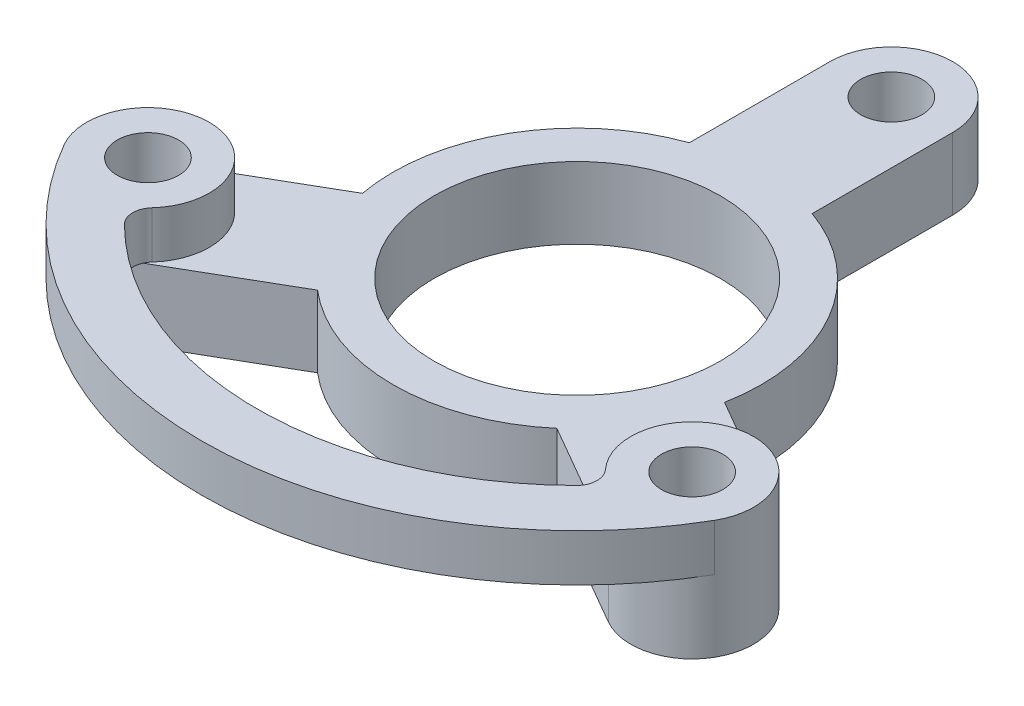
SolidWorks part; units mm, degrees
ref_plane "Front" through (0, 0, 0) normal (0, 0, 1) x (1, 0, 0)
ref_plane "Top" through (0, 0, 0) normal (0, 1, 0) x (1, 0, 0)
ref_plane "Right" through (0, 0, 0) normal (1, 0, 0) x (0, 0, -1)
sketch "Sketch1" plane through (0, 0, 0) normal (0, 1, 0) x (1, 0, 0)
  line L0 (0, 15.3575) -> (-13.3, -7.6788) construction
  line L1 (-13.3, -7.6788) -> (13.3, -7.6788) construction
  line L2 (13.3, -7.6788) -> (0, 15.3575) construction
  line L3 (-3, 8.4853) -> (-3, 15.3575)
  line L4 (3, 8.4853) -> (3, 15.3575)
  line L5 (8.8485, -1.6446) -> (14.8, -5.0807)
  line L6 (5.8485, -6.8407) -> (11.8, -10.2768)
  line L7 (-5.8485, -6.8407) -> (-11.8, -10.2768)
  line L8 (-8.8485, -1.6446) -> (-14.8, -5.0807)
  circle A0 centre (0, 0) radius 9
  circle A1 centre (0, 0) radius 15.3575 construction
  circle A2 centre (0, 15.3575) radius 3
  circle A3 centre (-13.3, -7.6788) radius 3
  circle A4 centre (13.3, -7.6788) radius 3
  circle A5 centre (0, 0) radius 7
  circle A6 centre (0, 15.3575) radius 1.5
  circle A7 centre (13.3, -7.6788) radius 1.5
  circle A8 centre (-13.3, -7.6788) radius 1.5
  point P25 (0, 0)
  dimension "D1" = 18
  dimension "D2" = 6
  dimension "D5" = 14
  dimension "D6" = 3
  dimension "D3" = 26.6
  dimension "D4" = 3
extrude "Boss-Extrude1" add sketch "Sketch1" along normal blind 3.5 contours A0 A5 | A2 L3 A0 L4 | A2 A6 | A3 L7 A0 L8 | A3 A8 | A4 L5 A0 L6 | A4 A7 region at (0, 0, -10.9668) region at (0, 0, -8.7454) region at (0, 0, -18.2727) region at (-9.4976, 0, 5.4834) region at (-11.8424, 0, 5.1542) region at (9.4976, 0, 5.4834) region at (15.8246, 0, 6.2212)
sketch "Sketch2" plane through (0, 3.5, 0) normal (0, 1, 0) x (1, 0, 0)
  line L0 (-13.3, -7.6788) -> (-15.8981, -9.1788) construction
  line L1 (-13.3, -7.6788) -> (-10.7019, -6.1788) construction
  line L2 (-17.3629, -5.9605) -> (-11.688, -4.0124) construction
  line L3 (17.3629, -5.9605) -> (11.688, -4.0124) construction
  arc A0 (-15.8981, -9.1788) -> (15.8981, -9.1788) centre (0, 0) ccw
  arc A1 (-14.8, -5.0807) -> (-11.8, -10.2768) centre (-13.3, -7.6788) ccw construction
  arc A2 (-14.8, -5.0807) -> (-11.8, -10.2768) centre (-13.3, -7.6788) ccw
  arc A3 (-10.7019, -6.1788) -> (10.7019, -6.1788) centre (0, 0) ccw
  arc A4 (11.8, -10.2768) -> (14.8, -5.0807) centre (13.3, -7.6788) ccw construction
  arc A5 (11.8, -10.2768) -> (14.8, -5.0807) centre (13.3, -7.6788) ccw
  arc A6 (17.3629, -5.9605) -> (-17.3629, -5.9605) centre (0, 0) ccw construction
  arc A7 (11.688, -4.0124) -> (-11.688, -4.0124) centre (0, 0) ccw construction
  arc A8 (11.8, -10.2768) -> (-11.8, -10.2768) centre (0, 0) cw
  circle A9 centre (13.3, -7.6788) radius 3
  circle A10 centre (-13.3, -7.6788) radius 3
  arc A11 (-11.688, -4.0124) -> (-10.7019, -6.1788) centre (0, 0) ccw construction
  arc A12 (-17.3629, -5.9605) -> (-15.8981, -9.1788) centre (0, 0) ccw construction
  arc A13 (15.8981, -9.1788) -> (17.3629, -5.9605) centre (0, 0) ccw construction
  arc A14 (10.7019, -6.1788) -> (11.688, -4.0124) centre (0, 0) ccw construction
  line M9 (5.8485, -6.8407) -> (11.8, -10.2768)
  arc M10 (11.8, -10.2768) -> (14.8, -5.0807) centre (13.3, -7.6788) ccw
  arc M18 (-14.8, -5.0807) -> (-11.8, -10.2768) centre (-13.3, -7.6788) ccw
  line M19 (-11.8, -10.2768) -> (-5.8485, -6.8407)
  circle M20 centre (13.3, -7.6788) radius 1.5
  circle M22 centre (-13.3, -7.6788) radius 1.5
extrude "Boss-Extrude2" add sketch "Sketch2" along normal blind 2.3 contours A0 M9 M19 M18 M10 | A10 M18 M22 | A9 M10 M20 region at (-14.1621, 3.5, 10.8962) region at (-16.1158, 3.5, 6.9243) region at (14.0545, 3.5, 10.4946)
fillet "Fillet2" radius 1 2 edges at (-11.8, 4.65, 10.2768) (11.8, 4.65, 10.2768)
